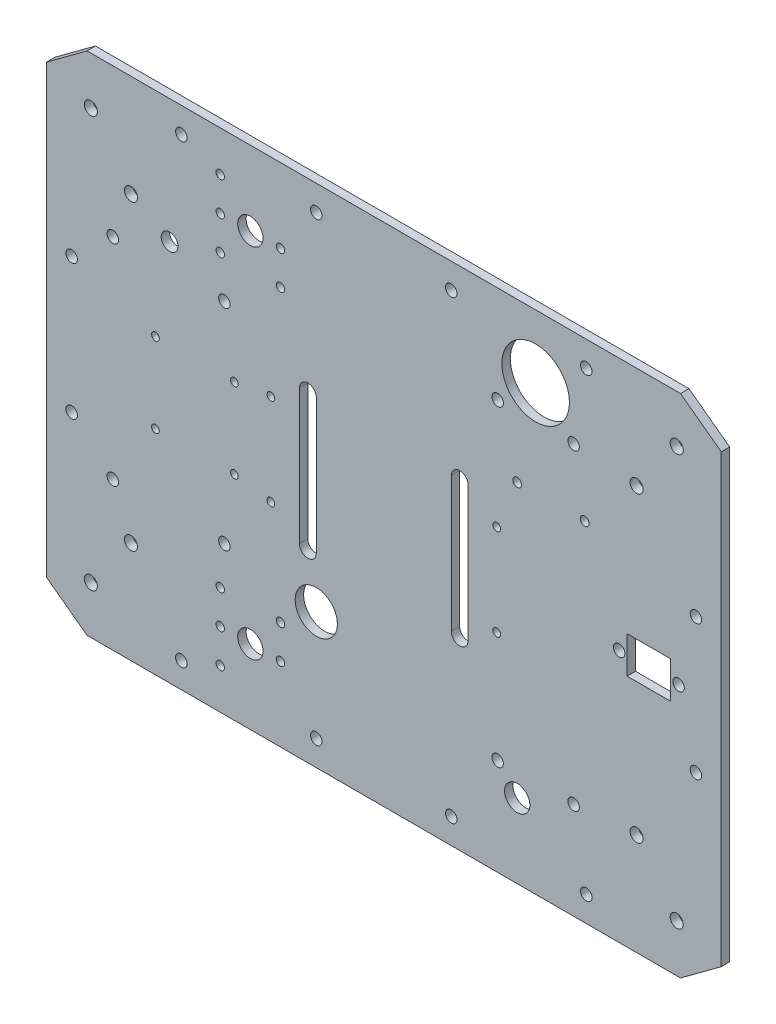
SolidWorks part; units mm, degrees
material "Thornel Mat VMA"
ref_plane "Front Plane" through (0, 0, 0) normal (0, 0, 1) x (1, 0, 0)
ref_plane "Top Plane" through (0, 0, 0) normal (0, 1, 0) x (1, 0, 0)
ref_plane "Right Plane" through (0, 0, 0) normal (1, 0, 0) x (0, 0, -1)
sketch "Sketch1" plane through (0, 0, 0) normal (0, 0, 1) x (1, 0, 0)
  line L0 (-127, 0) -> (127, 0) construction
  line L1 (0, -95.25) -> (0, 95.25) construction
  line L2 (-107.95, 0) -> (-107.95, 41.011) construction
  line L3 (-107.95, 41.011) -> (-95.25, 41.011) construction
  line L4 (-95.25, 41.011) -> (-79.9365, 52.3423) construction
  line L5 (-79.9365, 52.3423) -> (-79.9365, 76.2) construction
  line L6 (-79.9365, 76.2) -> (0, 76.2) construction
  line L7 (-95.25, 41.011) -> (-127, 83.9186) construction
  line L8 (-79.9365, 52.3423) -> (-111.6865, 95.25) construction
  line L9 (-111.6865, -95.25) -> (-127, -83.9186)
  line L10 (111.6865, -95.25) -> (127, -83.9186)
  line L11 (111.6865, 95.25) -> (127, 83.9186)
  line L12 (-87.5933, 46.6767) -> (-95.1475, 56.8856) construction
  line L13 (-95.1475, 56.8856) -> (-110.256, 77.3036) construction
  line L24 (127, -83.9186) -> (127, 83.9186)
  line L26 (111.6865, 95.25) -> (-111.6865, 95.25)
  line L27 (-111.6865, 95.25) -> (-127, 83.9186)
  line L28 (-127, 83.9186) -> (-127, -83.9186)
  line L30 (-111.6865, -95.25) -> (111.6865, -95.25)
  circle A0 centre (-95.1475, 56.8856) radius 2.4638
  circle A1 centre (-110.256, 77.3036) radius 2.4638
  circle A2 centre (110.256, 77.3036) radius 2.4638
  circle A3 centre (95.1475, 56.8856) radius 2.4638
  circle A4 centre (-110.256, -77.3036) radius 2.4638
  circle A5 centre (-95.1475, -56.8856) radius 2.4638
  circle A6 centre (110.256, -77.3036) radius 2.4638
  circle A7 centre (95.1475, -56.8856) radius 2.4638
  point P12 (0, 0)
  dimension "D1" = 190.5
  dimension "D2" = 254
  dimension "D3" = 19.05
  dimension "D4" = 19.05
  dimension "D5" = 12.7
  dimension "D6" = 19.05
  dimension "D7" = 143.5
  dimension "D8" = 12.7
  dimension "D9" = 25.4
extrude "Boss-Extrude1" add sketch "Sketch1" along normal blind 3.175
sketch "Sketch2" plane through (0, 0, 3.175) normal (0, 0, 1) x (1, 0, 0)
  line L0 (-127, 0) -> (127, 0) construction
  line L1 (-127, 83.9186) -> (-127, -83.9186) construction
  line L2 (127, -83.9186) -> (127, 83.9186) construction
  line L3 (57.15, 65.0875) -> (57.15, -65.0875) construction
  line L4 (38.1, 65.0875) -> (76.2, 65.0875)
  line L5 (38.1, 65.0875) -> (38.1, -65.0875)
  line L6 (38.1, -65.0875) -> (76.2, -65.0875)
  line L7 (76.2, 65.0875) -> (76.2, -65.0875)
  line L8 (38.1, 65.0875) -> (76.2, -65.0875) construction
  line L9 (38.1, -65.0875) -> (76.2, 65.0875) construction
  line L10 (57.15, 58.7375) -> (47.625, 58.7375) construction
  line L11 (47.625, 58.7375) -> (38.1, 58.7375) construction
  line L12 (99.7726, 0) -> (99.7726, 35.1373) construction
  line L13 (91.5811, -6.9215) -> (107.9641, -6.9215)
  line L14 (91.5811, -6.9215) -> (91.5811, 6.9215)
  line L15 (91.5811, 6.9215) -> (107.9641, 6.9215)
  line L16 (107.9641, -6.9215) -> (107.9641, 6.9215)
  line L17 (91.5811, -6.9215) -> (107.9641, 6.9215) construction
  line L18 (91.5811, 6.9215) -> (107.9641, -6.9215) construction
  circle A0 centre (42.8625, 58.7375) radius 2.159
  circle A1 centre (42.8625, -58.7375) radius 2.159
  circle A2 centre (71.4375, -58.7375) radius 2.159
  circle A3 centre (71.4375, 58.7375) radius 2.159
  circle A4 centre (110.9486, 0) radius 2.159
  circle A5 centre (88.5966, 0) radius 2.159
  point P6 (57.15, 0)
  point P17 (42.8625, 58.7375)
  point P25 (99.7726, 0)
  dimension "D6" = 13.843
  dimension "D8" = 11.176
  dimension "D1" = 38.1
  dimension "D2" = 130.175
  dimension "D3" = 6.35
  dimension "D4" = 9.525
  dimension "D5" = 69.85
  dimension "D7" = 16.383
extrude "Cut-Extrude1" cut sketch "Sketch2" against normal through all contours A1 | A2 | A3 | A0 | L13 L16 L15 L14 | A5 | A4 region at (99.7726, 0, 3.175) region at (42.8625, 58.7375, 3.175) region at (42.8625, -58.7375, 3.175) region at (71.4375, -58.7375, 3.175) region at (71.4375, 58.7375, 3.175) region at (110.9486, 0, 3.175) region at (88.5966, 0, 3.175)
sketch "Sketch3" plane through (0, 0, 3.175) normal (0, 0, 1) x (1, 0, 0)
  line L0 (0, 95.25) -> (0, -95.25) construction
  line L1 (111.6865, 95.25) -> (-111.6865, 95.25) construction
  line L2 (-111.6865, -95.25) -> (111.6865, -95.25) construction
  line L3 (127, 0) -> (-127, 0) construction
  line L4 (127, -83.9186) -> (127, 83.9186) construction
  line L5 (-127, 83.9186) -> (-127, -83.9186) construction
  line L8 (119.3433, -89.5843) -> (111.789, -79.3753) construction
  line L10 (111.6865, -95.25) -> (127, -83.9186) construction
  line L11 (111.6865, -95.25) -> (127, -83.9186)
  circle A0 centre (111.789, -79.3753) radius 1.9844
  circle A1 centre (96.6805, -58.9574) radius 1.9844
  point P21 (1.9415, -31.8445)
  dimension "D2" = 3.9688
  dimension "D3" = 3.9688
  dimension "D1" = 12.7
  dimension "D4" = 25.4
sketch "Sketch5" plane through (0, 0, 0) normal (0, 0, -1) x (-1, 0, 0)
  line L0 (-127, 0) -> (127, 0) construction
  line L1 (105.9946, 43.5) -> (55.9947, 43.5) construction
  line L2 (105.9946, 43.5) -> (105.9946, -43.5) construction
  line L3 (105.9946, -43.5) -> (55.9947, -43.5) construction
  line L4 (55.9947, 43.5) -> (55.9947, -43.5) construction
  line L5 (89.2369, 18.0341) -> (89.2369, -18.0339)
  line L6 (67.8946, 95.25) -> (67.8946, -95.25) construction
  line L7 (-71.4375, 58.7375) -> (-42.8625, 58.7375) construction
  line L8 (0, 64.0679) -> (0, -49.8393) construction
  line L9 (-42.5, 17.2) -> (42.5, 17.2) construction
  line L10 (-42.5, 17.2) -> (-42.5, -17.2) construction
  line L11 (-42.5, -17.2) -> (42.5, -17.2) construction
  line L12 (42.5, 17.2) -> (42.5, -17.2) construction
  line L13 (-42.5, 17.2) -> (42.5, -17.2) construction
  line L14 (-42.5, -17.2) -> (42.5, 17.2) construction
  line L15 (80.5946, 60.96) -> (31.75, 60.96) construction
  line L16 (61.5446, -67.31) -> (-87.4336, -67.31) construction
  line L17 (50.2154, -67.31) -> (50.2154, 67.31) construction
  line L18 (50.2154, 67.31) -> (38.8861, 67.31) construction
  line L19 (-28.575, 25.4) -> (-28.575, -25.4) construction
  line L20 (-111.6865, 95.25) -> (111.6865, 95.25) construction
  line L21 (-127, -83.9186) -> (-127, 83.9186) construction
  line L22 (-57.15, 71.4375) -> (80.5946, 71.4375) construction
  line L23 (80.5946, 71.4375) -> (80.5946, 48.58) construction
  line L25 (80.5946, -77.0458) -> (80.5946, 48.58) construction
  line L26 (127, 0) -> (-127, 0) construction
  line L27 (80.9947, 0) -> (80.9947, -8419.0368) construction
  line L28 (-25.4, 25.4) -> (-25.4, -25.4)
  line L29 (-31.75, 25.4) -> (-31.75, -25.4)
  line L30 (28.575, 25.4) -> (28.575, -25.4) construction
  line L31 (25.4, 25.4) -> (25.4, -25.4)
  line L32 (31.75, 25.4) -> (31.75, -25.4)
  line L33 (71.0787, 0) -> (71.0787, 12.3782) construction
  line L34 (53.2197, 18.0341) -> (89.2369, 18.0341)
  line L35 (53.2197, 18.0341) -> (53.2197, -18.0339)
  line L36 (53.2197, -18.0339) -> (89.2369, -18.0339)
  line L40 (-57.15, 58.7375) -> (-57.15, 95.25) construction
  circle A0 centre (61.5446, -54.61) radius 1.5875
  circle A1 centre (61.5446, -67.31) radius 1.5875
  circle A2 centre (80.5946, 48.58) radius 3.175
  circle A3 centre (-57.15, 71.4375) radius 12.7
  circle A4 centre (61.5446, 54.61) radius 1.5875
  circle A5 centre (61.5446, -80.01) radius 1.5875
  circle A6 centre (-50.2154, -67.31) radius 4.7625
  circle A7 centre (50.2154, -67.31) radius 4.7625
  circle A8 centre (61.5446, 67.31) radius 1.5875
  circle A9 centre (61.5446, 80.01) radius 1.5875
  circle A10 centre (50.2154, 67.31) radius 4.7625
  circle A11 centre (-50.2154, 35.56) radius 1.651
  circle A12 centre (59.9952, 39.4995) radius 2.159
  circle A13 centre (101.9941, 39.4995) radius 2.159
  circle A14 centre (59.9952, -39.4995) radius 2.159
  circle A15 centre (101.9941, -39.4995) radius 2.159
  circle A16 centre (38.8861, 67.31) radius 1.5875
  circle A17 centre (38.8861, 54.61) radius 1.5875
  circle A18 centre (38.8861, -67.31) radius 1.5875
  circle A19 centre (38.8861, -54.61) radius 1.5875
  arc A20 (-25.4, 25.4) -> (-31.75, 25.4) centre (-28.575, 25.4) ccw
  arc A21 (-31.75, -25.4) -> (-25.4, -25.4) centre (-28.575, -25.4) ccw
  arc A22 (25.4, 25.4) -> (31.75, 25.4) centre (28.575, 25.4) cw
  arc A23 (31.75, -25.4) -> (25.4, -25.4) centre (28.575, -25.4) cw
  circle A24 centre (56.2197, 15.0341) radius 1.4478
  circle A25 centre (56.2197, -15.0341) radius 1.4478
  circle A26 centre (85.9377, -15.0341) radius 1.4478
  circle A27 centre (85.9377, 15.0341) radius 1.4478
  circle A28 centre (-42.5, 17.2) radius 1.4542
  circle A29 centre (-42.5, -17.2) radius 1.4541
  circle A30 centre (42.5, -17.2) radius 1.4541
  circle A31 centre (42.5, 17.2) radius 1.4542
  circle A32 centre (-75.6154, 35.6276) radius 1.651
  point P0 (80.9947, 0)
  point P9 (0, 0)
  point P77 (-28.575, 0)
  point P84 (28.575, 0)
  point P89 (71.0787, 0)
  dimension "D10" = 6.35
  dimension "D15" = 2.9997
  dimension "D17" = 3.302
  dimension "D18" = 3.302
  dimension "D25" = 4.0005
  dimension "D45" = 2.8956
  dimension "D9" = 59.69
  dimension "D13" = 14.859
  dimension "D14" = 3
  dimension "D8" = 111.76
  dimension "D1" = 87.0001
  dimension "D2" = 49.9999
  dimension "D4" = 34.4
  dimension "D5" = 85
  dimension "D6" = 6.35
  dimension "D7" = 12.7
  dimension "D11" = 5.08
  dimension "D12" = 25.4
  dimension "D16" = 25.4
  dimension "D26" = 4.0005
  dimension "D38" = 50.8
  dimension "D39" = 6.35
  dimension "D40" = 28.575
  dimension "D41" = 36.0172
  dimension "D42" = 36.068
  dimension "D44" = 3
extrude "Cut-Extrude2" cut sketch "Sketch5" against normal through all contours A3 | A2 | A14 | A15 | A13 | A12 | L29 A21 L28 A20 | A23 L4 A22 L31 | A23 L32 A22 L4 | A27 | A24 | A25 | A26
sketch "Sketch6" plane through (0, 0, 0) normal (0, 0, -1) x (-1, 0, 0)
  line L0 (0, 0) -> (-135.1326, 0) construction
  line L1 (0, 0) -> (0, -95.25) construction
  line L2 (111.6865, -95.25) -> (-111.6865, -95.25) construction
  line L3 (-76.2, -95.25) -> (-76.2, -85.725) construction
  line L4 (117.475, 0) -> (117.475, -25.4) construction
  line L5 (127, 0) -> (-127, 0) construction
  line L6 (127, 83.9186) -> (127, -83.9186) construction
  circle A0 centre (-76.2, -85.725) radius 2.159
  circle A1 centre (-25.4, -85.725) radius 2.159
  circle A2 centre (25.4, -85.725) radius 2.159
  circle A3 centre (76.2, -85.725) radius 2.159
  circle A4 centre (76.2, 85.725) radius 2.159
  circle A5 centre (25.4, 85.725) radius 2.159
  circle A6 centre (-25.4, 85.725) radius 2.159
  circle A7 centre (-76.2, 85.725) radius 2.159
  circle A8 centre (117.475, -25.4) radius 2.159
  circle A9 centre (117.475, 25.4) radius 2.159
  circle A10 centre (-117.475, 25.4) radius 2.159
  circle A11 centre (-117.475, -25.4) radius 2.159
  dimension "D2" = 9.525
  dimension "D3" = 76.2
  dimension "D5" = 9.525
  dimension "D6" = 25.4
  dimension "D4" = 4
extrude "Cut-Extrude3" cut sketch "Sketch6" against normal through all
extrude "Cut-Extrude4" cut sketch "Sketch5<3>" against normal through all contours A28 | A29 | A31 | A30
sketch "Sketch5<3>" plane through (0, 0, 0) normal (0, 0, -1) x (-1, 0, 0) same geometry as "Sketch5"
extrude "Cut-Extrude5" cut sketch "Sketch5<4>" against normal through all contours A10 | A9 | A8 | A4 | A0 | A1 | A5 | A7 | A6
sketch "Sketch5<4>" plane through (0, 0, 0) normal (0, 0, -1) x (-1, 0, 0) same geometry as "Sketch5"
extrude "Cut-Extrude6" cut sketch "Sketch5<5>" against normal blind 2.54 contours A18 | A17 | A16
sketch "Sketch5<5>" plane through (0, 0, 0) normal (0, 0, -1) x (-1, 0, 0) same geometry as "Sketch5"
extrude "Cut-Extrude7" cut sketch "Sketch5<6>" against normal through all contours A17 | A18 | A16
sketch "Sketch5<6>" plane through (0, 0, 0) normal (0, 0, -1) x (-1, 0, 0) same geometry as "Sketch5"
sketch "Sketch8" plane through (0, 0, 3.175) normal (0, 0, 1) x (1, 0, 0)
extrude "Cut-Extrude8" cut sketch "Sketch5<7>" against normal blind 2.54 contours A11
sketch "Sketch5<7>" plane through (0, 0, 0) normal (0, 0, -1) x (-1, 0, 0) same geometry as "Sketch5"
extrude "Cut-Extrude9" cut sketch "Sketch5<9>" against normal blind 2.54 contours A11 | A32
sketch "Sketch5<9>" plane through (0, 0, 0) normal (0, 0, -1) x (-1, 0, 0) same geometry as "Sketch5"
extrude "Cut-Extrude13" cut sketch "Sketch5<12>" against normal through all both and the other way through all contours A11 | A32
sketch "Sketch5<12>" plane through (0, 0, 0) normal (0, 0, -1) x (-1, 0, 0) same geometry as "Sketch5"
extrude "Cut-Extrude14" cut sketch "Sketch5<13>" against normal through all contours A19
sketch "Sketch5<13>" plane through (0, 0, 0) normal (0, 0, -1) x (-1, 0, 0) same geometry as "Sketch5"
sketch "Sketch9" plane through (0, 0, 3.175) normal (0, 0, 1) x (1, 0, 0)
  line L1 (-127, 83.9186) -> (-127, -83.9186) construction
  line L2 (-111.6865, -95.25) -> (111.6865, -95.25) construction
  circle A1 centre (-25.4, -44.45) radius 7.9375
  dimension "D1" = 101.6
  dimension "D2" = 50.8
extrude "Cut-Extrude15" cut sketch "Sketch9" against normal through all both and the other way through all contours A1 region at (-25.4, -44.45, 3.175)
